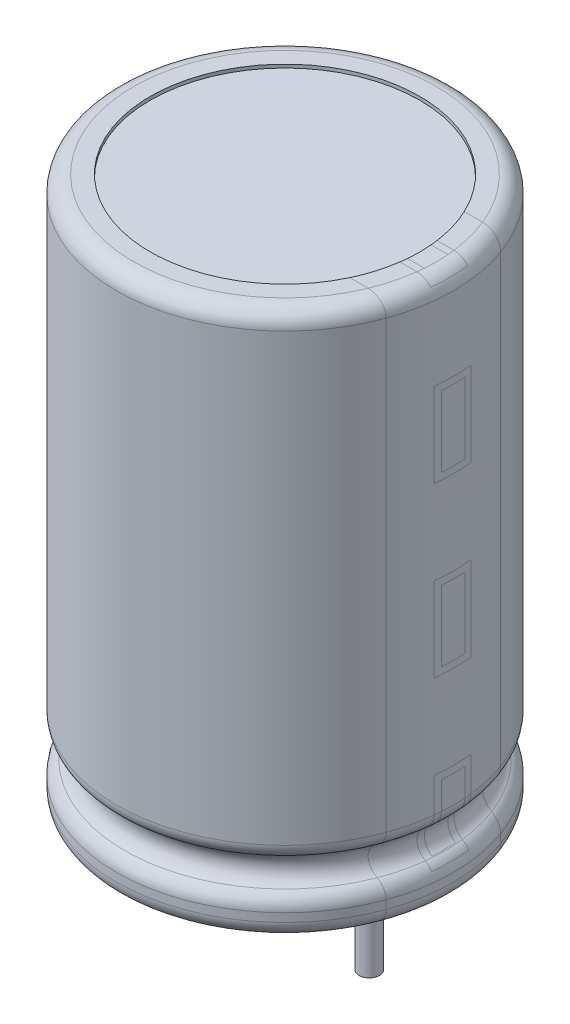
SolidWorks part; units mm, degrees
ref_plane "Front Plane" through (0, 0, 0) normal (0, 0, 1) x (1, 0, 0)
ref_plane "Top Plane" through (0, 0, 0) normal (0, 1, 0) x (1, 0, 0)
ref_plane "Right Plane" through (0, 0, 0) normal (1, 0, 0) x (0, 0, -1)
sketch "Sketch1" plane through (0, 0, 0) normal (0, 1, 0) x (1, 0, 0)
  line L0 (0, 0) -> (0, 44.7542) construction
  line L1 (0, 0) -> (-44.7542, 0) construction
  circle A0 centre (-2.5, 0) radius 0.3
  circle A1 centre (2.5, 0) radius 0.3
  dimension "D3" = 0.6
  dimension "D1" = 2.5
extrude "Boss-Extrude1" add sketch "Sketch1" against normal blind 3 and the other way blind 1
sketch "Sketch3" plane through (0, 0, 0) normal (0, 0, 1) x (1, 0, 0)
  line L1 (0, 0.1) -> (0, 16.2) construction
  line L2 (5, 0.5) -> (5, 0.75)
  line L3 (0, 0.1) -> (4, 0.1)
  line L4 (4, 16.2) -> (4.5, 16.2)
  line L5 (4, 0) -> (4.5, 0)
  line L6 (0, 16.1) -> (4, 16.1)
  line L7 (5, 2.4821) -> (5, 15.7)
  line L8 (4, 16.1) -> (4, 16.2)
  line L9 (5, 2.4821) -> (5, 16.2) construction
  line L10 (4, 0) -> (4, 0.1)
  line L11 (0, 16.1) -> (5, 16.1) construction
  line L12 (0, 16.2) -> (5, 16.2) construction
  line L13 (4, 2.4821) -> (4, 16.2) construction
  line L14 (0, 0.1) -> (0, 16.1)
  line L17 (0, 0.1) -> (5, 0.1) construction
  line L18 (0, 0) -> (5, 0) construction
  arc A0 (4.75, 2.049) -> (4.75, 1.183) centre (5, 1.616) ccw
  arc A1 (5, 0.75) -> (4.75, 1.183) centre (4.5, 0.75) ccw
  arc A2 (5, 2.4821) -> (4.75, 2.049) centre (4.5, 2.4821) cw
  arc A3 (5, 15.7) -> (4.5, 16.2) centre (4.5, 15.7) ccw
  arc A4 (4.5, 0) -> (5, 0.5) centre (4.5, 0.5) ccw
  point P13 (5, 2.116)
  point P29 (0, 20.1)
  point P30 (0, 0.1126)
  point P31 (0.1319, 0.1)
  point P32 (4.5, 1.616)
  point P33 (0.118, 20.2)
  point P35 (0, 0)
  point P36 (0.1461, 20.2)
  point P37 (-8.5502, 0.1)
  dimension "D2" = 0.5
  dimension "D1" = 0.5
  dimension "D9" = 0.5
  dimension "D3" = 16
  dimension "D6" = 5
  dimension "D7" = 0.1
  dimension "D8" = 8
  dimension "D10" = 0.25
  dimension "D11" = 9
  dimension "D5" = 1
revolve "Revolve1" add sketch "Sketch3" angle 360 about L14
sketch "Sketch4" plane through (0, 0, 0) normal (1, 0, 0) x (0, 0, -1)
  line L0 (-4.5, 0) -> (4.5, 0) construction
  line L1 (-1.7, 0) -> (1.7, 0)
  line L2 (0, 0) -> (0, 16.2) construction
  line L3 (-1.7, 16.2) -> (1.7, 16.2)
  line L4 (1.7, 0) -> (1.7, 16.2)
  line L5 (4, 16.2) -> (-4, 16.2) construction
  line L6 (-1.7, 0) -> (-1.7, 16.2)
  line L7 (-0.35, 13.3) -> (-0.35, 11.2)
  line L8 (-0.35, 13.3) -> (0.35, 13.3)
  line L9 (0, 13.3) -> (0, 11.2) construction
  line L10 (-0.35, 11.2) -> (0.35, 11.2)
  line L11 (0.35, 13.3) -> (0.35, 11.2)
  line L12 (0.55, 13.5) -> (0.55, 11)
  line L13 (-0.55, 11) -> (0.55, 11)
  line L14 (-0.55, 13.5) -> (-0.55, 11)
  line L15 (-0.55, 13.5) -> (0.55, 13.5)
  line L16 (0, 0) -> (0, -3.7489) construction
  line L17 (-0.35, 8.3) -> (-0.35, 6.2)
  line L18 (-0.35, 8.3) -> (0.35, 8.3)
  line L19 (-0.35, 6.2) -> (0.35, 6.2)
  line L20 (0.35, 8.3) -> (0.35, 6.2)
  line L21 (0.55, 8.5) -> (0.55, 6)
  line L22 (-0.55, 6) -> (0.55, 6)
  line L23 (-0.55, 8.5) -> (-0.55, 6)
  line L24 (-0.55, 8.5) -> (0.55, 8.5)
  line L25 (0, 8.3) -> (0, 6.2) construction
  line L26 (-0.35, 3.3) -> (-0.35, 1.2)
  line L27 (-0.35, 3.3) -> (0.35, 3.3)
  line L28 (-0.35, 1.2) -> (0.35, 1.2)
  line L29 (0.35, 3.3) -> (0.35, 1.2)
  line L30 (0.55, 3.5) -> (0.55, 1)
  line L31 (-0.55, 1) -> (0.55, 1)
  line L32 (-0.55, 3.5) -> (-0.55, 1)
  line L33 (-0.55, 3.5) -> (0.55, 3.5)
  line L34 (0, 3.3) -> (0, 1.2) construction
  line L35 (-0.55, 18.5) -> (0.55, 18.5)
  line L36 (-0.55, 18.5) -> (-0.55, 16)
  line L37 (-0.35, 18.3) -> (0.35, 18.3)
  line L38 (0.35, 18.3) -> (0.35, 16.2)
  line L39 (0.55, 18.5) -> (0.55, 16)
  line L40 (-0.35, 18.3) -> (-0.35, 16.2)
  line L41 (-0.35, 16.2) -> (0.35, 16.2)
  line L42 (-0.55, 16) -> (0.55, 16)
  line L51 (-0.55, 11) -> (-0.55, 8.5) construction
  line L52 (-0.55, 13.5) -> (-0.55, 16) construction
  point P20 (0, 0)
  point P23 (-0.6552, 20.4867)
  point P64 (0, 18.3)
  dimension "D5" = 3.4
  dimension "D6" = 0.2
  dimension "D7" = 1.1
  dimension "D8" = 2.1
  dimension "D1" = 0.7
  dimension "D9" = 1
  dimension "D10" = 2.5
  dimension "D2" = 3
  dimension "D3" = 2
split line "Split Line1"
